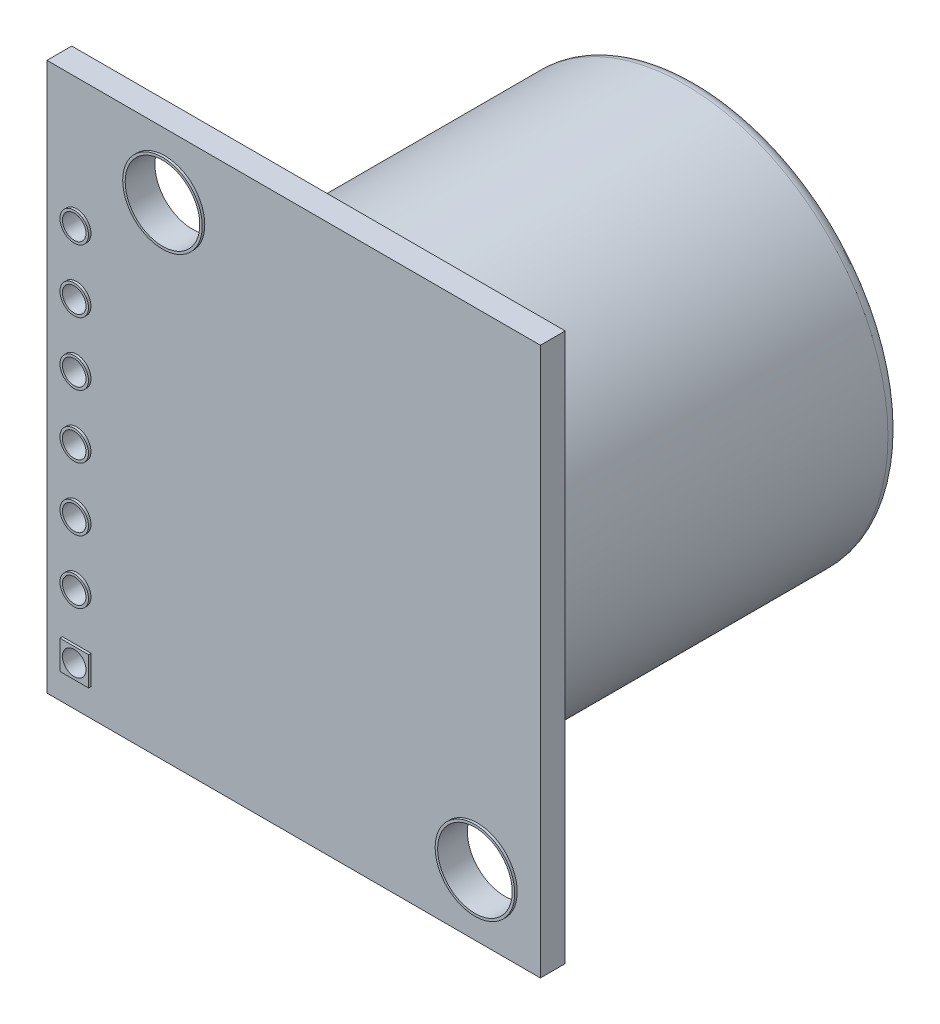
SolidWorks part; units mm, degrees
ref_plane "Front Plane" through (0, 0, 0) normal (0, 0, 1) x (1, 0, 0)
ref_plane "Top Plane" through (0, 0, 0) normal (0, 1, 0) x (1, 0, 0)
ref_plane "Right Plane" through (0, 0, 0) normal (1, 0, 0) x (0, 0, -1)
sketch "Sketch1" plane through (0, 0, 0) normal (0, 0, 1) x (1, 0, 0)
  line L0 (7.41, -6.4011) -> (7.41, 49993.5989) construction
  line L1 (-9.95, 11.05) -> (9.95, 11.05)
  line L2 (-9.95, 11.05) -> (-9.95, -11.05)
  line L3 (-9.95, -11.05) -> (9.95, -11.05)
  line L4 (9.95, 11.05) -> (9.95, -11.05)
  line L5 (-9.95, 11.05) -> (9.95, -11.05) construction
  line L6 (-9.95, -11.05) -> (9.95, 11.05) construction
  line L7 (7.41, -8.51) -> (50007.41, -8.51) construction
  line L8 (-5.221, 8.49) -> (49994.779, 8.49) construction
  line L9 (-5.19, 8.49) -> (-5.19, -49991.51) construction
  line L10 (-9.95, -9.35) -> (49990.05, -9.35) construction
  line L11 (-8.75, -9.35) -> (-8.75, -50009.35) construction
  circle A0 centre (-5.19, 8.49) radius 1.55
  circle A1 centre (7.41, -8.51) radius 1.55
  circle A2 centre (-8.75, -9.35) radius 0.5
  circle A3 centre (-8.75, -6.81) radius 0.5
  circle A4 centre (-8.75, -4.27) radius 0.5
  circle A5 centre (-8.75, -1.73) radius 0.5
  circle A6 centre (-8.75, 0.81) radius 0.5
  circle A7 centre (-8.75, 3.35) radius 0.5
  circle A8 centre (-8.75, 5.89) radius 0.5
  point P0 (0, 0)
  dimension "D7" = 3.1
  dimension "D10" = 1
  dimension "D1" = 22.1
  dimension "D2" = 19.9
  dimension "D3" = 2.54
  dimension "D4" = 2.54
  dimension "D5" = 17
  dimension "D6" = 12.6
  dimension "D8" = 1.7
  dimension "D9" = 18.7
  dimension "D11" = 7
extrude "Boss-Extrude1" add sketch "Sketch1" along normal blind 1
ref_plane "Plane1" through (0, 0, -0.3) normal (0, 0, -1) x (-1, 0, 0)
sketch "Sketch2" plane through (0, 0, -0.3) normal (0, 0, -1) x (-1, 0, 0)
  circle A0 centre (-0.5659, -0.3265) radius 8.2
  dimension "D1" = 16.4
extrude "Boss-Extrude2" add sketch "Sketch2" along normal blind 14.4 separate body
fillet "Fillet1" radius 0.5 1 edges at (-7.6341, -0.3265, -14.7)
shell "Shell1" thickness 0.1 removed face at (-7.6341, -0.3265, -0.3) removed face at (-7.1341, -0.3265, -14.7)
sketch "Sketch3" plane through (0, 0, 0) normal (0, 0, -1) x (-1, 0, 0)
  line L1 (9.3311, -9.9311) -> (8.1689, -9.9311)
  line L2 (9.3311, -9.9311) -> (9.3311, -8.7689)
  line L3 (9.3311, -8.7689) -> (8.1689, -8.7689)
  line L4 (8.1689, -9.9311) -> (8.1689, -8.7689)
  line L5 (9.3311, -9.9311) -> (8.1689, -8.7689) construction
  line L6 (9.3311, -8.7689) -> (8.1689, -9.9311) construction
  circle A0 centre (-7.41, -8.51) radius 1.505
  circle A1 centre (5.19, 8.49) radius 1.505
  circle A2 centre (8.75, 5.89) radius 0.475
  circle A3 centre (8.75, 3.35) radius 0.475
  circle A4 centre (8.75, 0.81) radius 0.475
  circle A5 centre (8.75, -1.73) radius 0.475
  circle A6 centre (8.75, -4.27) radius 0.475
  circle A7 centre (8.75, -6.81) radius 0.475
  circle A8 centre (8.75, -9.35) radius 0.475
  circle A9 centre (-7.41, -8.51) radius 1.605
  circle A10 centre (5.19, 8.49) radius 1.605
  circle A11 centre (8.75, 5.89) radius 0.575
  circle A12 centre (8.75, 3.35) radius 0.575
  circle A13 centre (8.75, 0.81) radius 0.575
  circle A14 centre (8.75, -1.73) radius 0.575
  circle A15 centre (8.75, -4.27) radius 0.575
  circle A16 centre (8.75, -6.81) radius 0.575
  dimension "D1" = 0.1
  dimension "D2" = 1.15
  dimension "D3" = 3.01
  dimension "D4" = 3.01
  dimension "D5" = 0.95
extrude "Boss-Extrude3" add sketch "Sketch3" along normal blind 0.1 and the other way blind 1.1
sketch "Sketch4" plane through (0, 0, 0) normal (0, 0, -1) x (-1, 0, 0)
  circle A0 centre (-0.5659, -0.3265) radius 7.7 construction
  circle A1 centre (-0.5659, -0.3265) radius 6.4226
extrude "Boss-Extrude4" add sketch "Sketch4" along normal blind 8 separate body
sketch "Sketch5" plane through (0, 0, -8) normal (0, 0, -1) x (-1, 0, 0)
  circle A0 centre (-0.5659, -0.3265) radius 4.7693
extrude "Cut-Extrude1" cut sketch "Sketch5" against normal blind 1
sketch "Sketch6" plane through (0, 0, -7) normal (0, 0, -1) x (-1, 0, 0)
  circle A0 centre (-0.5659, -0.3265) radius 4.6693
  circle A1 centre (-0.5659, -0.3265) radius 4.7693 construction
  dimension "D1" = 0.1
extrude "Boss-Extrude5" add sketch "Sketch6" along normal blind 3
fillet "Fillet2" radius 0.5 1 edges at (-4.1034, -0.3265, -10)
ref_plane "Plane2" through (0, 0, -14.7) normal (0, 0, -1) x (-1, 0, 0)
sketch "Sketch7" plane through (0, 0, -14.7) normal (0, 0, -1) x (-1, 0, 0)
  line L0 (-0.5659, -0.3265) -> (-0.5659, 49999.6735) construction
  line L1 (-0.5659, -0.3265) -> (-50000.5659, -0.3265) construction
  line L4 (-6.6607, -2.4267) -> (-6.7547, -2.4609)
  line L5 (-2.6661, -6.4213) -> (-2.7004, -6.5153)
  line L6 (1.5344, -6.4213) -> (1.5686, -6.5153)
  line L7 (5.5289, -2.4267) -> (5.623, -2.4609)
  line L8 (5.5289, 1.7738) -> (5.623, 1.808)
  line L9 (1.5344, 5.7683) -> (1.5686, 5.8624)
  line L10 (-2.6661, 5.7683) -> (-2.7004, 5.8624)
  line L11 (-6.6607, 1.7738) -> (-6.7547, 1.808)
  line L12 (-2.9934, -4.277) -> (-3.0459, -4.3625)
  line L13 (1.871, -4.283) -> (1.921, -4.3697)
  line L14 (3.3847, -2.754) -> (3.4701, -2.8065)
  line L15 (3.3907, 2.1104) -> (3.4774, 2.1604)
  line L16 (-4.5164, 2.1011) -> (-4.6019, 2.1536)
  line L17 (-4.5224, -2.7633) -> (-4.6091, -2.8134)
  line L18 (1.8617, 3.6241) -> (1.9142, 3.7095)
  line L19 (-3.0027, 3.6301) -> (-3.0528, 3.7168)
  line L20 (-6.6607, 1.7738) -> (-6.6493, 1.7699) construction
  line L21 (-1.4881, -3.0003) -> (-1.5209, -3.0956)
  line L22 (2.1082, -1.248) -> (2.2035, -1.2808)
  line L23 (0.3563, -3.0003) -> (0.3892, -3.0956)
  line L24 (1.5227, -6.3821) -> (1.5686, -6.5153) construction
  line L25 (5.5175, -2.4228) -> (5.5289, -2.4267) construction
  line L26 (-3.24, -1.248) -> (-3.3352, -1.2808)
  line L27 (-2.7004, 5.8624) -> (-2.6544, 5.7292) construction
  line L28 (-3.24, 0.595) -> (-3.3352, 0.6278)
  line L29 (0.3563, 2.3474) -> (0.3892, 2.4426)
  line L30 (2.1082, 0.595) -> (2.2035, 0.6278)
  line L31 (-1.4881, 2.3474) -> (-1.5209, 2.4426)
  circle A0 centre (-0.5659, -0.3265) radius 7.7
  circle A3 centre (-0.5659, -0.3265) radius 7.7 construction
  arc A9 (2.0291, -6.7199) -> (5.8276, -2.9215) centre (-0.5659, -0.3265) ccw
  arc A10 (1.7315, -5.9773) -> (5.085, -2.6238) centre (-0.5659, -0.3265) ccw
  arc A11 (-6.9593, -2.9215) -> (-6.7547, -2.4609) centre (-6.635, -2.7898) cw
  arc A12 (-2.7004, -6.5153) -> (-3.1609, -6.7199) centre (-3.0292, -6.3956) cw
  arc A13 (1.5344, -6.4213) -> (1.7315, -5.9773) centre (1.8633, -6.3016) cw
  arc A14 (5.5289, -2.4267) -> (5.085, -2.6238) centre (5.4092, -2.7556) ccw
  arc A15 (1.5686, -6.5153) -> (2.0291, -6.7199) centre (1.8975, -6.3956) ccw
  arc A16 (5.8276, -2.9215) -> (5.623, -2.4609) centre (5.5033, -2.7898) ccw
  arc A17 (-6.6607, -2.4267) -> (-6.2167, -2.6238) centre (-6.541, -2.7556) cw
  arc A18 (-2.6661, -6.4213) -> (-2.8632, -5.9773) centre (-2.995, -6.3016) ccw
  arc A19 (-2.8632, -5.9773) -> (-6.2167, -2.6238) centre (-0.5659, -0.3265) cw
  arc A20 (-3.1609, -6.7199) -> (-6.9593, -2.9215) centre (-0.5659, -0.3265) cw
  arc A21 (-3.1609, 6.067) -> (-6.9593, 2.2685) centre (-0.5659, -0.3265) ccw
  arc A22 (-2.8632, 5.3244) -> (-6.2167, 1.9709) centre (-0.5659, -0.3265) ccw
  arc A23 (-2.6661, 5.7683) -> (-2.8632, 5.3244) centre (-2.995, 5.6486) cw
  arc A24 (-6.6607, 1.7738) -> (-6.2167, 1.9709) centre (-6.541, 2.1027) ccw
  arc A25 (5.8276, 2.2685) -> (5.623, 1.808) centre (5.5033, 2.1369) cw
  arc A26 (1.5686, 5.8624) -> (2.0291, 6.067) centre (1.8975, 5.7427) cw
  arc A27 (5.5289, 1.7738) -> (5.085, 1.9709) centre (5.4092, 2.1027) cw
  arc A28 (1.5344, 5.7683) -> (1.7315, 5.3244) centre (1.8633, 5.6486) ccw
  arc A29 (-2.7004, 5.8624) -> (-3.1609, 6.067) centre (-3.0292, 5.7427) ccw
  arc A30 (-6.9593, 2.2685) -> (-6.7547, 1.808) centre (-6.635, 2.1369) ccw
  arc A31 (1.7315, 5.3244) -> (5.085, 1.9709) centre (-0.5659, -0.3265) cw
  arc A32 (2.0291, 6.067) -> (5.8276, 2.2685) centre (-0.5659, -0.3265) cw
  arc A33 (3.9643, -2.6691) -> (3.9632, 2.0182) centre (-0.5659, -0.3265) ccw
  arc A34 (3.2568, -2.2955) -> (3.2547, 1.6467) centre (-0.5659, -0.3265) ccw
  arc A35 (3.3907, 2.1104) -> (3.2547, 1.6467) centre (3.5657, 1.8073) ccw
  arc A36 (3.4774, 2.1604) -> (3.9632, 2.0182) centre (3.6524, 1.8573) cw
  arc A37 (3.3847, -2.754) -> (3.2568, -2.2955) centre (3.5679, -2.4558) cw
  arc A38 (3.9643, -2.6691) -> (3.4701, -2.8065) centre (3.6534, -2.5083) cw
  arc A39 (-2.9085, -4.8566) -> (-3.0459, -4.3625) centre (-2.7477, -4.5457) cw
  arc A40 (-2.9934, -4.277) -> (-2.535, -4.1491) centre (-2.6952, -4.4603) cw
  arc A41 (-2.535, -4.1491) -> (1.4073, -4.147) centre (-0.5659, -0.3265) ccw
  arc A42 (-2.9085, -4.8566) -> (1.7788, -4.8555) centre (-0.5659, -0.3265) ccw
  arc A43 (1.871, -4.283) -> (1.4073, -4.147) centre (1.5679, -4.458) ccw
  arc A44 (1.921, -4.3697) -> (1.7788, -4.8555) centre (1.6179, -4.5447) cw
  arc A45 (-5.096, 2.0162) -> (-4.6019, 2.1536) centre (-4.7851, 1.8554) cw
  arc A46 (-4.5164, 2.1011) -> (-4.3885, 1.6426) centre (-4.6997, 1.8029) cw
  arc A47 (-4.3885, 1.6426) -> (-4.3864, -2.2996) centre (-0.5659, -0.3265) ccw
  arc A48 (-5.096, 2.0162) -> (-5.0949, -2.6712) centre (-0.5659, -0.3265) ccw
  arc A49 (-4.5224, -2.7633) -> (-4.3864, -2.2996) centre (-4.6974, -2.4602) ccw
  arc A50 (-4.6091, -2.8134) -> (-5.0949, -2.6712) centre (-4.7841, -2.5103) cw
  arc A51 (1.7767, 4.2037) -> (1.9142, 3.7095) centre (1.616, 3.8928) cw
  arc A52 (1.8617, 3.6241) -> (1.4032, 3.4962) centre (1.5635, 3.8073) cw
  arc A53 (1.4032, 3.4962) -> (-2.539, 3.4941) centre (-0.5659, -0.3265) ccw
  arc A54 (1.7767, 4.2037) -> (-2.9106, 4.2026) centre (-0.5659, -0.3265) ccw
  arc A55 (-3.0027, 3.6301) -> (-2.539, 3.4941) centre (-2.6996, 3.8051) ccw
  arc A56 (-3.0528, 3.7168) -> (-2.9106, 4.2026) centre (-2.7497, 3.8918) cw
  circle A57 centre (-0.5659, -0.3265) radius 1
  arc A60 (0.5333, -2.5719) -> (1.6798, -1.4251) centre (-0.5659, -0.3265) ccw
  arc A61 (0.8726, -3.2964) -> (2.4045, -1.7642) centre (-0.5659, -0.3265) ccw
  arc A62 (0.8726, -3.2964) -> (0.3892, -3.0956) centre (0.72, -2.9814) cw
  arc A63 (0.3563, -3.0003) -> (0.5333, -2.5719) centre (0.6872, -2.8862) cw
  arc A64 (2.1082, -1.248) -> (1.6798, -1.4251) centre (1.9942, -1.5789) ccw
  arc A65 (2.2035, -1.2808) -> (2.4045, -1.7642) centre (2.0894, -1.6117) cw
  arc A66 (-3.3352, -1.2808) -> (-3.5362, -1.7642) centre (-3.2212, -1.6117) ccw
  arc A67 (-3.24, -1.248) -> (-2.8116, -1.4251) centre (-3.126, -1.5789) cw
  arc A68 (-1.4881, -3.0003) -> (-1.6651, -2.5719) centre (-1.8189, -2.8862) ccw
  arc A69 (-2.0044, -3.2964) -> (-1.5209, -3.0956) centre (-1.8518, -2.9814) ccw
  arc A70 (-2.0044, -3.2964) -> (-3.5362, -1.7642) centre (-0.5659, -0.3265) cw
  arc A71 (-1.6651, -2.5719) -> (-2.8116, -1.4251) centre (-0.5659, -0.3265) cw
  arc A72 (-1.6651, 1.9189) -> (-2.8116, 0.7721) centre (-0.5659, -0.3265) ccw
  arc A73 (-2.0044, 2.6435) -> (-3.5362, 1.1112) centre (-0.5659, -0.3265) ccw
  arc A74 (-2.0044, 2.6435) -> (-1.5209, 2.4426) centre (-1.8518, 2.3285) cw
  arc A75 (-1.4881, 2.3474) -> (-1.6651, 1.9189) centre (-1.8189, 2.2333) cw
  arc A76 (-3.24, 0.595) -> (-2.8116, 0.7721) centre (-3.126, 0.9259) ccw
  arc A77 (-3.3352, 0.6278) -> (-3.5362, 1.1112) centre (-3.2212, 0.9588) cw
  arc A78 (2.2035, 0.6278) -> (2.4045, 1.1112) centre (2.0894, 0.9588) ccw
  arc A79 (2.1082, 0.595) -> (1.6798, 0.7721) centre (1.9942, 0.9259) cw
  arc A80 (0.3563, 2.3474) -> (0.5333, 1.9189) centre (0.6872, 2.2333) ccw
  arc A81 (0.8726, 2.6435) -> (0.3892, 2.4426) centre (0.72, 2.3285) ccw
  arc A82 (0.8726, 2.6435) -> (2.4045, 1.1112) centre (-0.5659, -0.3265) cw
  arc A83 (0.5333, 1.9189) -> (1.6798, 0.7721) centre (-0.5659, -0.3265) cw
  point P108 (-0.5659, -0.3265)
  point P119 (1.7977, -1.141)
  point P124 (2.5541, -1.4016)
  point P137 (-3.6858, -1.4016)
  point P138 (-2.9295, -1.141)
  point P163 (-2.9295, 0.488)
  point P164 (-3.6858, 0.7487)
  point P165 (2.5541, 0.7487)
  point P166 (1.7977, 0.488)
  dimension "D1" = 0.8
  dimension "D2" = 0.8
  dimension "D5" = 0.35
  dimension "D3" = 1
  dimension "D4" = 0.8
  dimension "D6" = 0.35
  dimension "D8" = 2
  dimension "D9" = 0.35
  dimension "D7" = 4
extrude "Boss-Extrude6" add sketch "Sketch7" against normal blind 0.1
